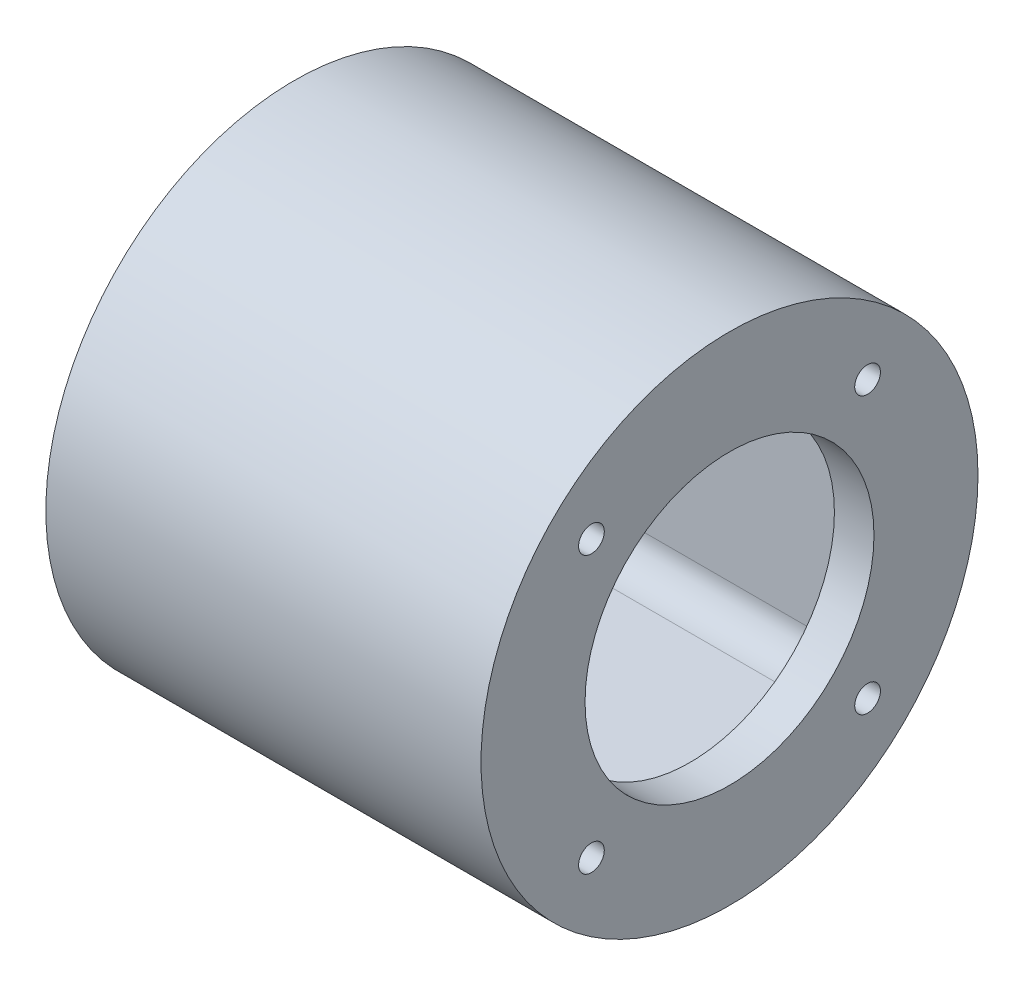
SolidWorks part; units mm, degrees
ref_plane "Front Plane" through (0, 0, 0) normal (0, 0, 1) x (1, 0, 0)
ref_plane "Top Plane" through (0, 0, 0) normal (0, 1, 0) x (1, 0, 0)
ref_plane "Right Plane" through (0, 0, 0) normal (1, 0, 0) x (0, 0, -1)
sketch "Sketch1" plane through (0, 0, 0) normal (1, 0, 0) x (0, 0, -1)
  line L1 (34.9, -43) -> (-34.9, -43)
  line L2 (43, -34.9) -> (43, 34.9)
  line L3 (34.9, 43) -> (-34.9, 43)
  line L4 (-43, -34.9) -> (-43, 34.9)
  line L5 (43, -43) -> (-43, 43) construction
  line L6 (43, 43) -> (-43, -43) construction
  circle A0 centre (0, 0) radius 36.5175
  circle A1 centre (-34.9, 34.9) radius 3.25
  circle A2 centre (34.9, 34.9) radius 3.25
  circle A3 centre (34.9, -34.9) radius 3.25
  circle A4 centre (-34.9, -34.9) radius 3.25
  circle A5 centre (0, 0) radius 62.8112
  circle A6 centre (0, 0) radius 60.8112 construction
  arc A7 (-43, -34.9) -> (-34.9, -43) centre (-34.9, -34.9) ccw
  arc A8 (-34.9, 43) -> (-43, 34.9) centre (-34.9, 34.9) ccw
  arc A9 (34.9, -43) -> (43, -34.9) centre (34.9, -34.9) ccw
  arc A10 (43, 34.9) -> (34.9, 43) centre (34.9, 34.9) ccw
  point P25 (45.6063, 40.3931)
  point P26 (32.6216, -43)
  point P27 (-151.5106, 189.2726)
  point P28 (-148.6448, 229.5831)
  point P29 (-146.9254, 239.5603)
  point P30 (-47.0825, -36.2516)
  dimension "D3" = 2
  dimension "D4" = 6.5
  dimension "D6" = 73.035
  dimension "D2" = 86
  dimension "D5" = 69.8
  dimension "D1" = 4
extrude "Boss-Extrude1" add sketch "Sketch1" along normal blind 10 contours L2 A10 L3 A8 L4 A7 L1 A9 A4 A3 A2 A1 A0 | A5 A10 L2 A9 L1 A7 L4 A8 L3 region at (0, -41.7838, 0) region at (0, 0, 61.0346)
extrude "Boss-Extrude2" add sketch "Sketch1<3>" against normal blind 100 contours A5 A10 L2 A9 L1 A7 L4 A8 L3 region at (0, 0, 61.0346)
sketch "Sketch1<3>" plane through (0, 0, 0) normal (1, 0, 0) x (0, 0, -1) same geometry as "Sketch1"
